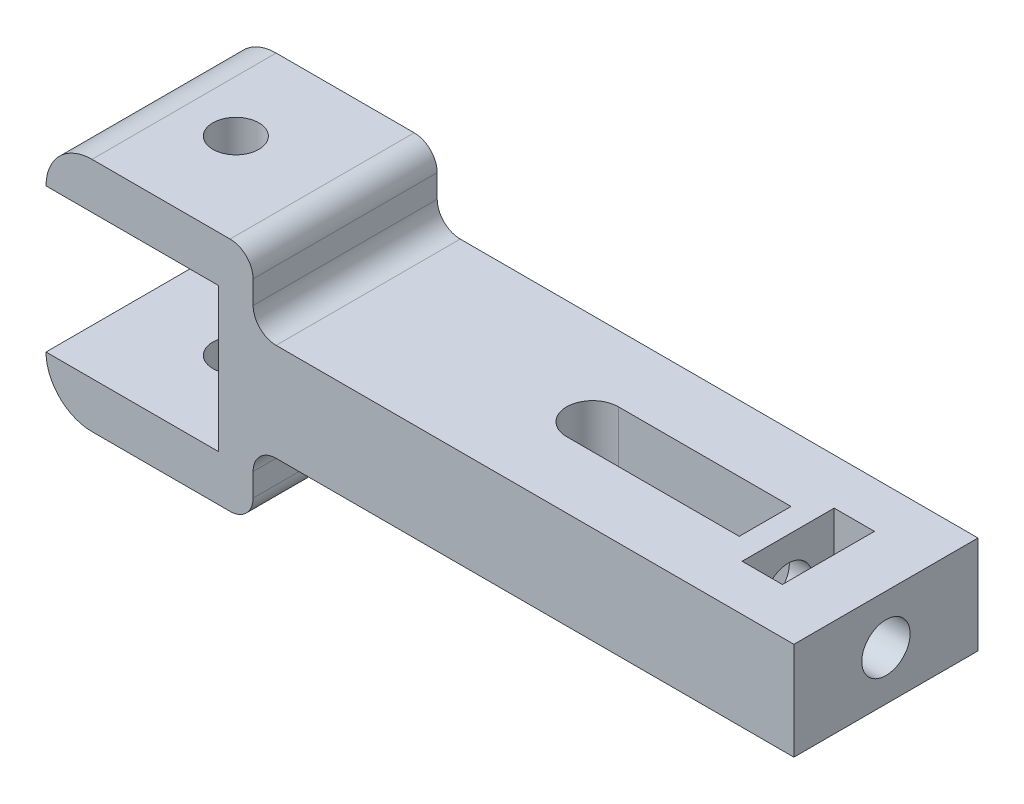
SolidWorks part; units mm, degrees
ref_plane "Front Plane" through (0, 0, 0) normal (0, 0, 1) x (1, 0, 0)
ref_plane "Top Plane" through (0, 0, 0) normal (0, 1, 0) x (1, 0, 0)
ref_plane "Right Plane" through (0, 0, 0) normal (1, 0, 0) x (0, 0, -1)
sketch "Sketch1" plane through (0, 0, 0) normal (0, 0, 1) x (1, 0, 0)
  line L0 (0, 0) -> (-47, 0)
  line L1 (-47, 0) -> (-47, 6)
  line L2 (-47, 6) -> (-65, 6)
  line L3 (-65, 6) -> (-65, 2)
  line L4 (-65, 2) -> (-50, 2)
  line L5 (-50, 2) -> (-50, -10.5)
  line L6 (0, 0) -> (0, -8.5)
  line L7 (0, -4.25) -> (-50, -4.25) construction
  line L8 (-65, -10.5) -> (-50, -10.5)
  line L9 (-65, -14.5) -> (-65, -10.5)
  line L10 (-47, -14.5) -> (-65, -14.5)
  line L11 (-47, -8.5) -> (-47, -14.5)
  line L12 (0, -8.5) -> (-47, -8.5)
  dimension "D1" = 65
  dimension "D2" = 15
  dimension "D3" = 4.25
  dimension "D4" = 6.25
  dimension "D5" = 4
  dimension "D6" = 18
extrude "Boss-Extrude1" add sketch "Sketch1" along normal blind 16
sketch "Sketch2" plane through (0, 0, 0) normal (0, 1, 0) x (1, 0, 0)
  line L0 (0, -8) -> (-47, -8) construction
  line L1 (0, -16) -> (0, 0) construction
  line L2 (-47, -16) -> (-47, 0) construction
  line L4 (-8.5, -4) -> (-5, -4)
  line L5 (-8.5, -4) -> (-8.5, -12)
  line L6 (-8.5, -12) -> (-5, -12)
  line L7 (-5, -4) -> (-5, -12)
  line L8 (-8.5, -4) -> (-5, -12) construction
  line L9 (-8.5, -12) -> (-5, -4) construction
  line L10 (-25.5, -10.25) -> (-10.5, -10.25)
  line L12 (-25.5, -5.75) -> (-10.5, -5.75)
  line L13 (-10.5, -10.25) -> (-10.5, -5.75)
  line L14 (-25.5, -10.25) -> (-10.5, -5.75) construction
  line L15 (-25.5, -5.75) -> (-10.5, -10.25) construction
  arc A0 (-25.5, -5.75) -> (-25.5, -10.25) centre (-25.5, -8) ccw
  point P6 (-6.75, -8)
  point P11 (-18, -8)
  dimension "D7" = 2.25
  dimension "D1" = 8
  dimension "D2" = 3.5
  dimension "D3" = 5
  dimension "D4" = 2
  dimension "D5" = 4.5
  dimension "D6" = 15
extrude "Cut-Extrude1" cut sketch "Sketch2" against normal through all
sketch "Sketch3" plane through (0, 0, 0) normal (1, 0, 0) x (0, 0, -1)
  line L0 (-8, 0) -> (-8, -8.5) construction
  line L1 (-16, 0) -> (0, 0) construction
  line L2 (-16, -8.5) -> (0, -8.5) construction
  circle A0 centre (-8, -4.25) radius 2.1
  dimension "D1" = 4.2
extrude "Cut-Extrude2" cut sketch "Sketch3" against normal up to surface (10.5 mm away) up to face at (-10.5, -4.25, 8)
fillet "Fillet1" radius 2 4 edges at (-47, -8.5, 8) (-47, 6, 8) (-47, 0, 8) (-47, -14.5, 8)
sketch "Sketch4" plane through (0, -10.5, 0) normal (0, 1, 0) x (1, 0, 0)
  line L0 (-65, -8) -> (-49, -8) construction
  line L1 (-65, -16) -> (-65, 0) construction
  line L2 (-49, 0) -> (-49, -16) construction
  circle A0 centre (-57, -8) radius 9
  dimension "D1" = 18
extrude "Cut-Extrude3" cut sketch "Sketch4" along normal up to surface (12.5 mm away) up to face at (-57.5, 2, 8)
sketch "Sketch5" plane through (0, 6, 0) normal (0, 1, 0) x (1, 0, 0)
  line L0 (-65, -8) -> (-49, -8) construction
  line L1 (-65, -16) -> (-65, 0) construction
  line L2 (-49, -16) -> (-49, 0) construction
  circle A0 centre (-56.5, -8) radius 2
  dimension "D1" = 4
  dimension "D2" = 8.5
extrude "Cut-Extrude4" cut sketch "Sketch5" against normal through all
fillet "Fillet2" radius 4 2 edges at (-65, -14.5, 8) (-65, 6, 8)
equation "\"X-ROD-SPACING\"=45"
equation "\"Y-ROD-SPACING\"=75"
equation "\"Z-ROD-SPACING\"=17.5"
equation "\"Y-BED-OFFSET\"=2"
equation "\"Y-BED-ROD-INSET\"=3.5"
equation "\"T-SLOT-NUT-FILLET-RADIUS\"=0.5"
equation "\"T-SLOT-SCREW-SHAFT-RADIUS\"=1.55"
equation "\"T-SLOT-SCREW-SHAFT-CUTOUT-LENGTH\"=11.0"
equation "\"T-SLOT-NUT-DEPTH\"=3.5"
equation "\"T-SLOT-NUT-WIDTH\"=2.85"
equation "\"T-SLOT-NUT-END-DISTANCE\"=8"
equation "\"ACRYLIC-THICKNESS\"=10"
equation "\"ACRYLIC-TAB-CUTOUT-SIZE\"=\"ACRYLIC-THICKNESS\"+\"ACRYLIC-TAB-TOLERANCE\"*2"
equation "\"ACRYLIC-TAB-WIDTH\"=\"ACRYLIC-THICKNESS\""
equation "\"ACRYLIC-M3-HOLE\"=2.9"
equation "\"SMOOTHROD-CAP-SCREW-DISTANCE\"=20"
equation "\"FRAME-WIDTH-INNER\"=370"
equation "\"NEMA17-HOLE-SPACING\"=31"
equation "\"NEMA17-CENTRAL-CUTOUT\"=22.5"
equation "\"Z-BRACKET-REACH\"=55"
equation "\"TOP-BRACKET-SPACING\"=40"
equation "\"SMOOTHROD-X-LENGTH\"=350"
equation "\"SMOOTHROD-Y-LENGTH\"=350"
equation "\"SMOOTHROD-Z-LENGTH\"=350"
equation "\"SMOOTHROD-TIGHTENING-HEADROOM\"=.25"
equation "\"LEADSCREW-Z-LENGTH\"=300"
equation "\"SCREW-HEAD-RADIUS\"=6"
equation "\"PRINTED-X-SMOOTHROD-DIAMETER\"=8.4"
equation "\"PRINTED-X-SMOOTHROD-CUTOUT\"=10"
equation "\"PRINTED-X-BASE-HEIGHT\"=10"
equation "\"PRINTED-LM8UU-CUTOUT-SIZE\"=15.5"
equation "\"PRINTED-LM8UU-CUTOUT-LENGTH\"=24.5"
equation "\"PRINTED-X-IDLER-HEIGHT\"=16"
equation "\"D1@Boss-Extrude1\"=\"PRINTED-X-IDLER-HEIGHT\""
